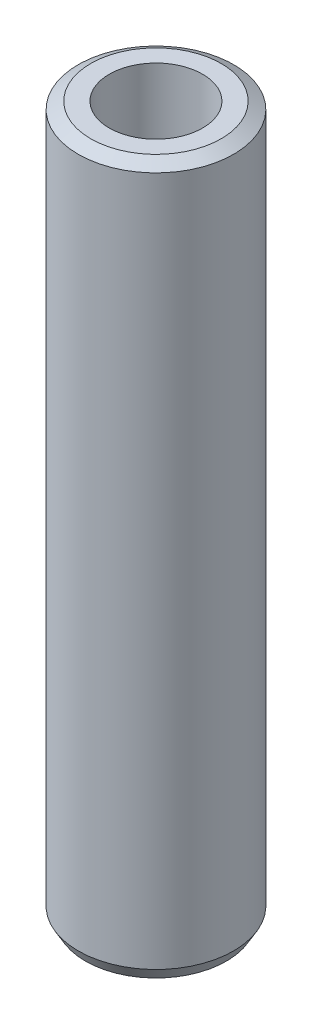
SolidWorks part; units mm, degrees
ref_plane "Front Plane" through (0, 0, 0) normal (0, 0, 1) x (1, 0, 0)
ref_plane "Top Plane" through (0, 0, 0) normal (0, 1, 0) x (1, 0, 0)
ref_plane "Right Plane" through (0, 0, 0) normal (1, 0, 0) x (0, 0, -1)
sketch "Sketch1" plane through (0, 0, 0) normal (0, 1, 0) x (1, 0, 0)
  circle A0 centre (0, 0) radius 10
  dimension "SHAFT_OD" = 20
extrude "Boss-Extrude1" add sketch "Sketch1" along normal blind 91.3014
sketch "Sketch2" plane through (0, 0, 0) normal (0, 1, 0) x (1, 0, 0)
  circle A0 centre (0, 0) radius 6.0069
  dimension "BORE_D" = 12.0137
extrude "Cut-Extrude1" cut sketch "Sketch2" along normal through all
chamfer "Chamfer1" distance 0.928 angle 60 2 edges at (0, 91.3014, 10) (0, 0, 10) first distance on face at (0, 91.3014, 10) first distance on face at (0, 0, 6.0069)
